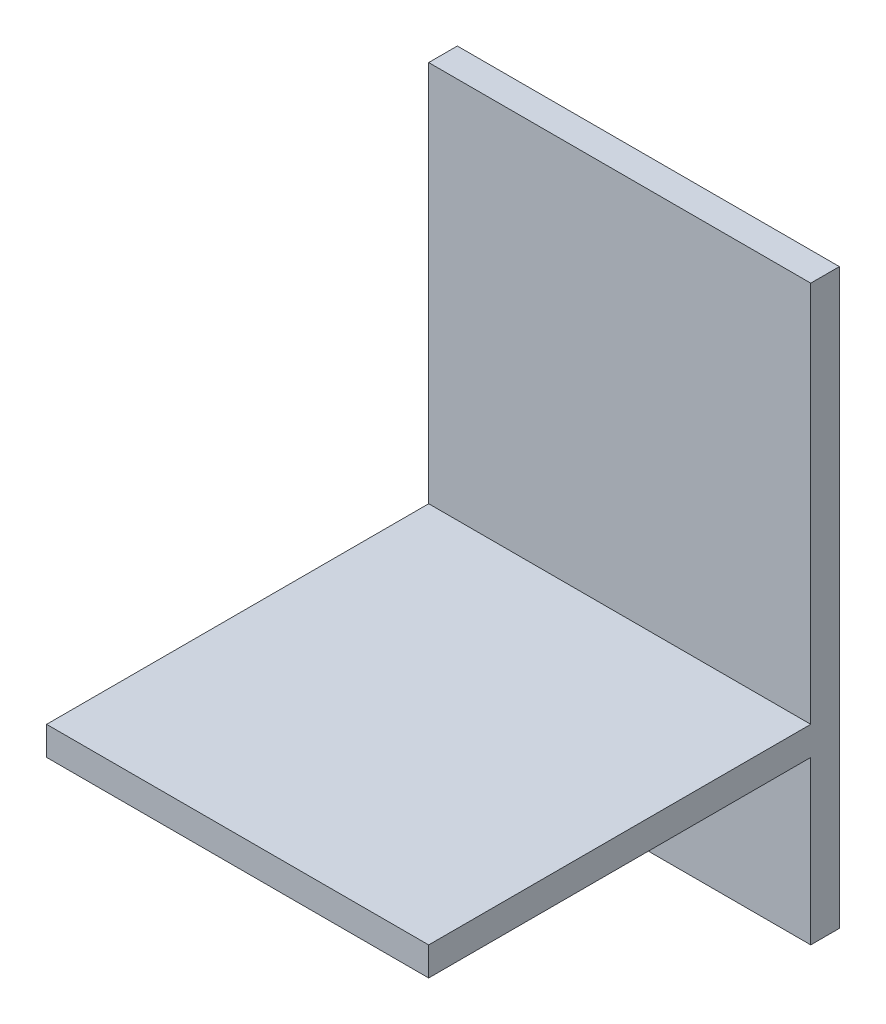
SolidWorks part; units mm, degrees
ref_plane "前视基准面" through (0, 0, 0) normal (0, 0, 1) x (1, 0, 0)
ref_plane "上视基准面" through (0, 0, 0) normal (0, 1, 0) x (1, 0, 0)
ref_plane "右视基准面" through (0, 0, 0) normal (1, 0, 0) x (0, 0, -1)
sketch "草图1" plane through (0, 0, 0) normal (0, 0, 1) x (1, 0, 0)
  line L1 (0, 0) -> (40, 0)
  line L2 (0, 0) -> (0, -60)
  line L3 (0, -60) -> (40, -60)
  line L4 (40, 0) -> (40, -60)
  dimension "D1" = 40
  dimension "D2" = 60
extrude "凸台-拉伸1" add sketch "草图1" along normal blind 3
sketch "草图2" plane through (0, 0, 3) normal (0, 0, 1) x (1, 0, 0)
  line L0 (0, 0) -> (0, -60) construction
  line L1 (0, -40) -> (40, -40)
  line L2 (0, -40) -> (0, -43)
  line L3 (0, -43) -> (40, -43)
  line L4 (40, -40) -> (40, -43)
  line L5 (40, 0) -> (40, -60) construction
  dimension "D1" = 3
  dimension "D2" = 40
extrude "凸台-拉伸2" add sketch "草图2" along normal blind 40
sketch "草图3" plane through (0, 0, 0) normal (-1, 0, 0) x (0, 0, 1)
  line L0 (3, -55) -> (28, -43)
  line L1 (28, -43) -> (3, -43)
  line L2 (3, -43) -> (3, -55)
  line L3 (3, -43) -> (3, -60) construction
  line L4 (43, -43) -> (3, -43) construction
  dimension "D1" = 25
  dimension "D2" = 12
extrude "凸台-拉伸3" add sketch "草图3" against normal blind 23
extrude "切除-拉伸1" cut sketch "草图3<2>" against normal blind 17
sketch "草图3<2>" plane through (0, 0, 0) normal (-1, 0, 0) x (0, 0, 1) same geometry as "草图3"
